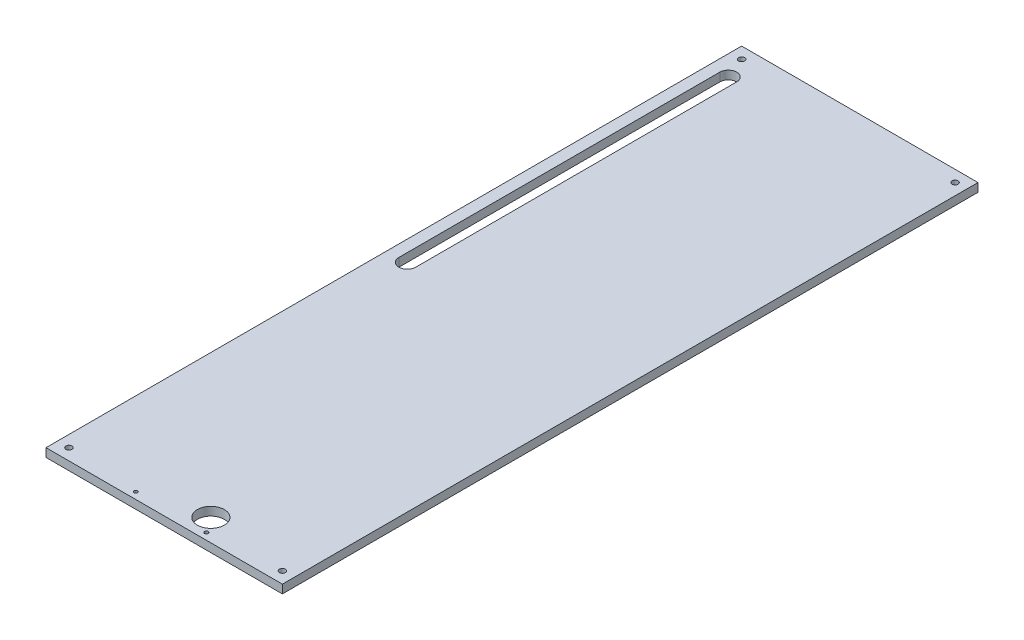
SolidWorks part; units mm, degrees
ref_plane "Front Plane" through (0, 0, 0) normal (0, 0, 1) x (1, 0, 0)
ref_plane "Top Plane" through (0, 0, 0) normal (0, 1, 0) x (1, 0, 0)
ref_plane "Right Plane" through (0, 0, 0) normal (1, 0, 0) x (0, 0, -1)
sketch "Sketch2" plane through (0, 0, 0) normal (0, 0, 1) x (1, 0, 0)
  line L0 (42.8242, -21.393) -> (42.8242, -24.5934)
  line L1 (0, -21.393) -> (0, -24.5934) construction
  line L2 (-46.0758, -24.5934) -> (42.8242, -24.5934)
  line L3 (-46.0758, -21.393) -> (-46.0758, -24.5934)
  line L4 (-46.0758, -21.393) -> (42.8242, -21.393)
  dimension "D1" = 88.9
  dimension "D2" = 3.2004
extrude "Boss-Extrude1" add sketch "Sketch2" along normal blind 261.62 contours L2 L0 L4 L3
sketch "Sketch3" plane through (0, -21.393, 0) normal (0, 1, 0) x (-1, 0, 0)
  line L0 (-42.8242, 259.08) -> (46.0758, 259.08) construction
  line L1 (38.5043, 9.421) -> (38.5043, 0) construction
  line L2 (46.0758, 0) -> (-42.8242, 0) construction
  line L3 (46.0758, 261.62) -> (-42.8242, 261.62) construction
  line L4 (41.7578, 257.302) -> (46.0758, 257.302) construction
  line L5 (46.0758, 72.9493) -> (41.6793, 72.9493) construction
  line L6 (35.3293, 12.596) -> (41.6793, 12.596) construction
  line L7 (35.3293, 12.596) -> (35.3293, 133.3026)
  line L8 (35.3293, 133.3026) -> (41.6793, 133.3026) construction
  line L9 (41.6793, 12.596) -> (41.6793, 133.3026)
  line L10 (46.0758, 261.62) -> (-42.8242, 261.62) construction
  line L11 (-11.6838, 259.08) -> (-11.6838, 261.62) construction
  line L12 (-11.6838, 253.3188) -> (-11.6838, 259.08) construction
  line L13 (-7.6198, 253.3188) -> (-11.6838, 253.3188) construction
  line L14 (-42.8242, 261.62) -> (-42.8242, 0) construction
  line L15 (46.0758, 261.62) -> (46.0758, 0) construction
  line L16 (-38.5062, 257.302) -> (-38.5062, 261.62) construction
  line L17 (-38.5062, 257.302) -> (-42.8242, 257.302) construction
  line L18 (41.7578, 257.302) -> (41.7578, 261.62) construction
  line L19 (-38.5062, 4.318) -> (-42.8242, 4.318) construction
  line L20 (-38.5062, 4.318) -> (-38.5062, 0) construction
  line L21 (46.0758, 0) -> (-42.8242, 0) construction
  line L22 (41.7578, 4.318) -> (41.7578, 0) construction
  line L23 (41.7578, 4.318) -> (46.0758, 4.318) construction
  circle A0 centre (14.8338, 259.08) radius 0.6731
  arc A1 (35.3293, 133.3026) -> (41.6793, 133.3026) centre (38.5043, 133.3026) cw
  arc A2 (41.6793, 12.596) -> (35.3293, 12.596) centre (38.5043, 12.596) cw
  circle A3 centre (-11.6838, 259.08) radius 0.6731
  circle A4 centre (-7.6198, 253.3188) radius 5.08
  circle A5 centre (-38.5062, 257.302) radius 1.1303
  circle A6 centre (41.7578, 257.302) radius 1.1303
  circle A7 centre (-38.5062, 4.318) radius 1.1303
  circle A8 centre (41.7578, 4.318) radius 1.1303
  point P12 (1.6258, 259.08)
  dimension "D5" = 1.3462
  dimension "D9" = 10.16
  dimension "D13" = 2.2606
  dimension "D2" = 4.3965
  dimension "D3" = 120.7066
  dimension "D4" = 6.35
  dimension "D6" = 2.54
  dimension "D7" = 26.5176
  dimension "D8" = 13.208
  dimension "D10" = 5.7612
  dimension "D11" = 4.064
  dimension "D12" = 9.421
  dimension "D14" = 4.318
extrude "Cut-Extrude1" cut sketch "Sketch3" against normal through all
